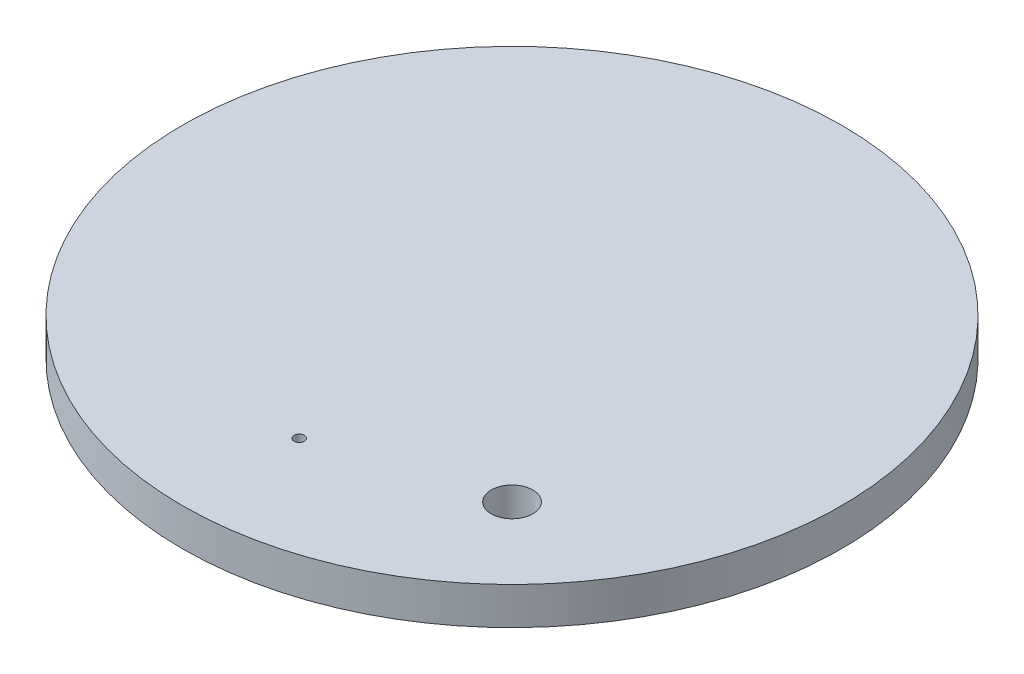
SolidWorks part; units mm, degrees
material "1060 Alloy"
ref_plane "Front Plane" through (0, 0, 0) normal (0, 0, 1) x (1, 0, 0)
ref_plane "Top Plane" through (0, 0, 0) normal (0, 1, 0) x (1, 0, 0)
ref_plane "Right Plane" through (0, 0, 0) normal (1, 0, 0) x (0, 0, -1)
sketch "Sketch1" plane through (0, 0, 0) normal (0, 1, 0) x (1, 0, 0)
  circle A0 centre (0, 0) radius 15.875
  dimension "D1" = 31.75
extrude "Boss-Extrude1" add sketch "Sketch1" along normal blind 1
sketch "Sketch2" plane through (0, 0, 0) normal (0, -1, 0) x (1, 0, 0)
  circle A0 centre (0, 0) radius 15.875
  circle A1 centre (0, 0) radius 9.525
  circle A2 centre (0, 0) radius 15.875 construction
  dimension "D1" = 0
  dimension "D2" = 19.05
extrude "Boss-Extrude2" add sketch "Sketch2" along normal blind 0.8
thread "Thread1" pitch 0.25 method cut profile "Thread Profile1" start angle 0, offset 0, length 1, pitch 0.25, diameter 19.05
ref_plane "Plane1" through (9.525, -0.8, 0) normal (0, 0, 1) x (1, 0, 0)
sketch "Thread Profile1" plane through (9.525, -0.8, 0) normal (0, 0, 1) x (1, 0, 0)
  line L0 (0, 0) -> (0, 0.25) construction
  line L1 (0, 0) -> (0.1353, 0.0781)
  line L2 (0.1353, 0.0781) -> (0.1353, 0.1094)
  line L3 (0.1353, 0.1094) -> (0, 0.1875)
  line L4 (0.1353, 0.0937) -> (0, 0.0937) construction
  line L11 (0, 0) -> (0, 0.1875)
  point P2 (0, 0)
  dimension "Pitch" = 0.25
  dimension "Profile_Angle" = 60
  dimension "Profile_Land" = 0.0312
  dimension "Profile_Height" = 0.1353
sketch "Sketch3" plane through (0, 1, 0) normal (0, 1, 0) x (1, 0, 0)
  circle A0 centre (0, -10.25) radius 0.25
  circle A1 centre (0, 0) radius 9.8
  dimension "D1" = 0.5
  dimension "D2" = 10.25
  dimension "D3" = 19.6
extrude "Cut-Extrude1" cut sketch "Sketch3" against normal through all both and the other way through all contours A1 A0 region at (0, 1, 10.25)
sketch "Sketch4" plane through (0, -0.8, 0) normal (0, -1, 0) x (1, 0, 0)
  line L0 (0, 0) -> (13.2597, 13.2597) construction
  circle A0 centre (7.7782, 7.7782) radius 1
  dimension "D2" = 2
  dimension "D1" = 11
extrude "Cut-Extrude2" cut sketch "Sketch4" against normal through all both and the other way through all
